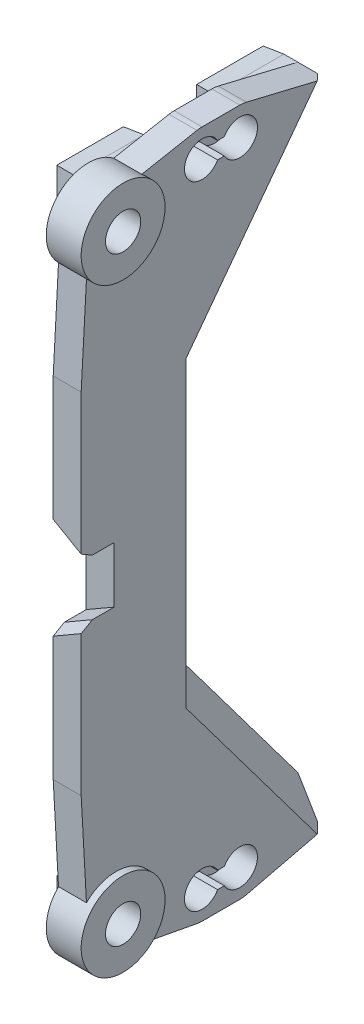
SolidWorks part; units mm, degrees
note: The reader was unsure of these and kept them because the rebuilt part matched: shared geometry of "Sketch11<2>".
ref_plane "Front Plane" through (0, 0, 0) normal (0, 0, 1) x (1, 0, 0)
ref_plane "Top Plane" through (0, 0, 0) normal (0, 1, 0) x (1, 0, 0)
ref_plane "Right Plane" through (0, 0, 0) normal (1, 0, 0) x (0, 0, -1)
sketch "SlideGeometry"
  dimension "D2" = 12.7
  dimension "D4" = 76.2
  dimension "D6" = 12.7
  dimension "D7" = 6.35
  dimension "D8" = 6.35
  dimension "D9" = 12.7
  dimension "D12" = 3.81
  dimension "D5" = 9.525
  dimension "D10" = 12.7
  dimension "D11" = 3.81
sketch_block_instance "PulleyOutline-1"
sketch_block "PulleyOutline" parameters "D1"=11.1125, "D2"=13.6525
sketch_block_instance "PulleyOutline-2"
sketch_block_instance "PulleyOutline-3"
sketch_block_instance "PulleyOutline-4"
sketch_block_instance "PulleyOutline-5"
sketch_block_instance "PulleyOutline-6"
sketch_block_instance "SlotOutline-1"
sketch_block "SlotOutline" parameters "D1"=6.35, "D2"=3
sketch_block_instance "SlotOutline-3"
sketch_block_instance "SlotOutline-4"
sketch "Sketch3" plane through (0, 0, 0) normal (1, 0, 0) x (0, 0, -1)
  circle A0 centre (-3.175, 27.2338) radius 3.81
  circle A1 centre (-3.175, 27.2338) radius 1.5 construction
  dimension "D1" = 7.62
  dimension "D2" = 3
extrude "DowelSupport" add sketch "Sketch3" along normal blind 1.905 and the other way blind 1.27
sketch "Sketch5" plane through (0, 0, 0) normal (1, 0, 0) x (0, 0, -1)
  line L1 (-6.35, -15.875) -> (3.175, -15.875)
  line L2 (-6.35, -15.875) -> (-6.35, 15.875)
  line L3 (-6.35, 15.875) -> (3.175, 15.875)
  line L4 (3.175, -15.875) -> (3.175, 15.875)
  line L5 (-6.35, -15.875) -> (3.175, 15.875) construction
  line L6 (-6.35, 15.875) -> (3.175, -15.875) construction
  point P0 (-1.5875, 0)
  dimension "D1" = 9.525
  dimension "D2" = 31.75
  dimension "D3" = 3.175
extrude "SliderDowelSupport" add sketch "Sketch5" along normal mid plane 2.54 separate body contours L3 L4 L1 L2
sketch "Sketch8" plane through (0, 0, 0) normal (1, 0, 0) x (0, 0, -1)
  line L0 (4.6355, 28.702) -> (8.0645, 28.702) construction
  line L1 (4.6355, 31.242) -> (8.0645, 31.242)
  line L2 (4.6355, 26.162) -> (8.0645, 26.162)
  line L3 (6.35, 31.75) -> (-6.35, 31.75) construction
  circle A0 centre (4.6355, 28.702) radius 1.5 construction
  circle A1 centre (8.0645, 28.702) radius 1.5 construction
  arc A2 (4.6355, 31.242) -> (4.6355, 26.162) centre (4.6355, 28.702) ccw
  arc A3 (5.7373, 29.7198) -> (5.5245, 28.702) centre (8.0645, 28.702) ccw construction
  arc A4 (8.0645, 31.242) -> (6.35, 30.5761) centre (8.0645, 28.702) ccw construction
  arc A5 (6.35, 30.5761) -> (4.6355, 31.242) centre (4.6355, 28.702) ccw construction
  arc A6 (6.35, 30.5761) -> (5.7373, 29.7198) centre (8.0645, 28.702) ccw construction
  arc A7 (6.9627, 29.7198) -> (6.35, 30.5761) centre (4.6355, 28.702) ccw construction
  arc A8 (7.1755, 28.702) -> (6.9627, 29.7198) centre (4.6355, 28.702) ccw construction
  arc A9 (6.9627, 27.6842) -> (7.1755, 28.702) centre (4.6355, 28.702) ccw construction
  arc A10 (6.35, 26.8279) -> (6.9627, 27.6842) centre (4.6355, 28.702) ccw construction
  arc A11 (5.7373, 27.6842) -> (6.35, 26.8279) centre (8.0645, 28.702) ccw construction
  arc A12 (8.0645, 26.162) -> (8.0645, 31.242) centre (8.0645, 28.702) ccw
  arc A13 (4.6355, 26.162) -> (6.35, 26.8279) centre (4.6355, 28.702) ccw construction
  arc A14 (6.35, 26.8279) -> (8.0645, 26.162) centre (8.0645, 28.702) ccw construction
  arc A15 (5.5245, 28.702) -> (5.7373, 27.6842) centre (8.0645, 28.702) ccw construction
  point P11 (6.35, 28.702)
  dimension "D1" = 3
  dimension "D3" = 5.08
  dimension "D2" = 3.429
  dimension "D4" = 0.508
  dimension "D5" = 9.525
extrude "StringDowelSupport" add sketch "Sketch8" along normal mid plane 2.54 separate body
sketch "Sketch9" plane through (0, 0, 0) normal (1, 0, 0) x (0, 0, -1)
  line B0 (3.175, 26.44) -> (-3.175, 26.44)
  line B1 (3.175, 26.44) -> (3.175, 29.44)
  line B2 (3.175, 29.44) -> (-3.175, 29.44)
  line B3 (-3.175, 26.44) -> (-3.175, 29.44)
  line B4 (3.175, 26.44) -> (-3.175, 29.44) construction
  line B5 (3.175, 29.44) -> (-3.175, 26.44) construction
  line B6 (15.875, 26.44) -> (9.525, 26.44)
  line B7 (15.875, 26.44) -> (15.875, 29.44)
  line B8 (15.875, 29.44) -> (9.525, 29.44)
  line B9 (9.525, 26.44) -> (9.525, 29.44)
sketch_block_instance "3DPTabGeo-1"
sketch_block "3DPTabGeo" parameters "D1"=3, "D2"=6.35
sketch_block_instance "3DPTabGeo-2"
extrude "TabSupport" add sketch "Sketch9" along normal mid plane 2.54
sketch "Sketch10" plane through (0, 0, 0) normal (1, 0, 0) x (0, 0, -1)
  line L0 (-6.35, 15.875) -> (-5.7111, 27.3747)
  line L1 (-5.7111, 27.3747) -> (-0.6389, 27.0928) construction
  line L2 (-6.35, 15.875) -> (3.175, 15.875)
  line L3 (3.175, 15.875) -> (3.175, 9.525)
  line L4 (3.175, 9.525) -> (15.875, 26.44)
  line L5 (15.875, 26.44) -> (15.875, 29.44)
  line L6 (15.875, 29.44) -> (8.6571, 31.1719)
  line L7 (8.6571, 31.1719) -> (4.1662, 31.1983)
  line L8 (4.1662, 31.1983) -> (-3.6443, 29.73)
  line L9 (-3.6443, 29.73) -> (-2.7057, 24.7375) construction
  line L10 (-5.7111, 27.3747) -> (-3.6443, 29.73)
  line L11 (3.175, -15.875) -> (3.175, 15.875) construction
  arc A0 (4.6355, 31.242) -> (4.6355, 26.162) centre (4.6355, 28.702) ccw construction
  arc A1 (8.0645, 26.162) -> (8.0645, 31.242) centre (8.0645, 28.702) ccw construction
  point P3 (-3.175, 27.2338)
  dimension "D1" = 5.08
  dimension "D2" = 6.35
extrude "InterSupport" add sketch "Sketch10" along normal mid plane 2.54
sketch "Sketch11" plane through (0, 0, 0) normal (1, 0, 0) x (0, 0, -1)
  line L1 (6.0424, 27.94) -> (6.6576, 27.94)
  line L2 (6.0424, 27.94) -> (6.0424, 29.464) construction
  line L3 (6.0424, 29.464) -> (6.6576, 29.464)
  line L4 (6.6576, 27.94) -> (6.6576, 29.464) construction
  line L5 (6.0424, 27.94) -> (6.6576, 29.464) construction
  line L6 (6.0424, 29.464) -> (6.6576, 27.94) construction
  circle A0 centre (-3.175, 27.2338) radius 1.6
  arc A1 (6.0424, 29.464) -> (6.0424, 27.94) centre (4.6355, 28.702) ccw
  arc A2 (6.6576, 27.94) -> (6.6576, 29.464) centre (8.0645, 28.702) ccw
  arc A3 (6.1771, 29.1303) -> (6.0424, 29.464) centre (4.6355, 28.702) ccw construction
  arc A4 (6.6576, 29.464) -> (6.5229, 29.1303) centre (8.0645, 28.702) ccw construction
  arc A5 (6.5229, 29.1303) -> (6.5229, 28.2737) centre (8.0645, 28.702) ccw construction
  arc A6 (6.1771, 28.2737) -> (6.1771, 29.1303) centre (4.6355, 28.702) ccw construction
  arc A7 (6.0424, 27.94) -> (6.1771, 28.2737) centre (4.6355, 28.702) ccw construction
  arc A8 (6.5229, 28.2737) -> (6.6576, 27.94) centre (8.0645, 28.702) ccw construction
  point P9 (6.35, 28.702)
  dimension "D1" = 3.2
  dimension "D3" = 1.524
extrude "DowelHoles" cut sketch "Sketch11" against normal through all both and the other way through all
extrude "Boss-Extrude1" add sketch "Sketch11<2>" along normal blind 0.254 from surface contours L1 A2 L3 A1 | A0
sketch "Sketch11<2>" plane through (0, 0, 0) normal (1, 0, 0) x (0, 0, -1) same geometry as "Sketch11"
sketch "Sketch14" plane through (-1.27, 0, 0) normal (-1, 0, 0) x (0, 0, 1)
  line B0 (-9.525, 26.44) -> (-15.875, 26.44)
  line B1 (-9.525, 26.44) -> (-9.525, 29.44)
  line B2 (-9.525, 29.44) -> (-15.875, 29.44)
  line B3 (-15.875, 26.44) -> (-15.875, 29.44)
  line B4 (-9.525, 29.44) -> (-15.875, 26.44) construction
  line B5 (3.175, 26.44) -> (-3.175, 26.44)
  line B6 (3.175, 26.44) -> (3.175, 29.44)
  line B7 (3.175, 29.44) -> (-3.175, 29.44)
  line B8 (-3.175, 26.44) -> (-3.175, 29.44)
sketch_block_instance "3DPTabGeo-3"
sketch_block_instance "3DPTabGeo-4"
extrude "TabBase" add sketch "Sketch14" along normal blind 1.27
sketch "Sketch15" plane through (-2.54, 0, 0) normal (-1, 0, 0) x (0, 0, 1)
  line L0 (-3.175, 29.44) -> (-3.175, 26.44) construction
  line L1 (-3.175, 26.44) -> (3.175, 26.44) construction
  line L2 (3.175, 26.44) -> (3.175, 29.44) construction
  line L3 (3.175, 29.44) -> (-3.175, 29.44) construction
  line L4 (-15.875, 29.44) -> (-15.875, 26.44) construction
  line L5 (-15.875, 26.44) -> (-9.525, 26.44) construction
  line L6 (-9.525, 26.44) -> (-9.525, 29.44) construction
  line L7 (-9.525, 29.44) -> (-15.875, 29.44) construction
  line L8 (-3.175, 29.44) -> (-3.175, 26.44)
  line L9 (-3.175, 26.44) -> (3.175, 26.44)
  line L10 (3.175, 26.44) -> (3.175, 29.44)
  line L11 (3.175, 29.44) -> (-3.175, 29.44)
  line L12 (-15.875, 29.44) -> (-15.875, 26.44)
  line L13 (-15.875, 26.44) -> (-9.525, 26.44)
  line L14 (-9.525, 26.44) -> (-9.525, 29.44)
  line L15 (-9.525, 29.44) -> (-15.875, 29.44)
extrude "TabDraft" add sketch "Sketch15" along normal offset from surface 3 draft 5
chamfer "Chamfer2" distance 2.54 angle 45 1 edges at (1.27, 17.9825, -9.525)
mirror "Mirror1" about plane through (0, 0, 0) normal (0, 1, 0) of bodies 118 115
sketch "Sketch16" plane through (0, 0, 6.35) normal (0, 0, 1) x (1, 0, 0)
  line L0 (-1.27, 4.0065) -> (-1.27, -4.0065)
  line L1 (-1.27, -15.875) -> (-1.27, 15.875) construction
  line L2 (-1.27, -4.0065) -> (1.27, -2.54)
  line L3 (1.27, -15.875) -> (1.27, 15.875) construction
  line L4 (1.27, -2.54) -> (1.27, 2.54)
  line L5 (1.27, 2.54) -> (-1.27, 4.0065)
  line L6 (0, 0) -> (3.5826, 0) construction
  dimension "D1" = 60
  dimension "D2" = 5.08
extrude "Cut-Extrude1" cut sketch "Sketch16" against normal blind 3
chamfer "Chamfer3" distance 0.508 distance2 1.016 2 edges at (0, -3.2732, 6.35) (0, 3.2732, 6.35)
equation "\"StageWidth\"= 2.5in"
equation "\"D1@SlideGeometry\" = \"StageWidth\""
equation "\"StageOffset\"= .5in"
equation "\"D3@SlideGeometry\" = \"StageWidth\" - \"StageOffset\""
equation "\"D4@SlideGeometry\" = \"StageWidth\" + \"StageOffset\""
equation "\"SlideOffset\"= 0.5in"
equation "\"D6@SlideGeometry\" = \"SlideOffset\""
equation "\"D7@SlideGeometry\" = \"StageOffset\" / 2"
equation "\"D8@SlideGeometry\" = \"StageOffset\" / 2"
equation "\"D9@SlideGeometry\" = \"SlideOffset\""
equation "\"OuterThickness\"= 0.1in"
equation "\"D1@SliderDowelSupport\"=\"OuterThickness\""
equation "\"D1@DowelSupport\"=\"OuterThickness\"/2+.025"
equation "\"DowelClearance\"= 3mm + .2mm"
equation "\"D1@TabSupport\" = \"OuterThickness\""
equation "\"D1@InterSupport\" = \"OuterThickness\""
equation "\"D1@Sketch11\"=\"DowelClearance\""
equation "\"D2@Sketch11\"=\"DowelClearance\""
equation "\"SliderDowelLength\"= 1"
equation "\"D2@Sketch5\"=\"SliderDowelLength\"+.25in"
equation "\"D11@SlideGeometry\"=\"D12@SlideGeometry\""
equation "\"D2@DowelSupport\"=\"OuterThickness\"/2"
